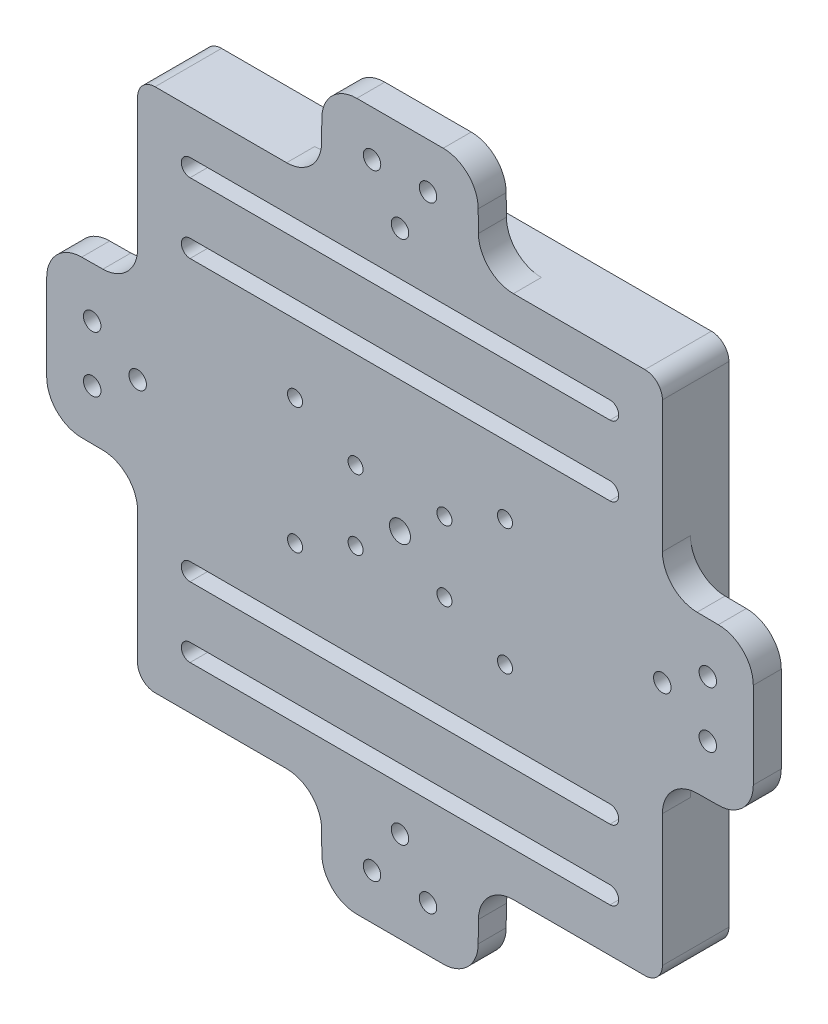
SolidWorks part; units mm, degrees
ref_plane "Front Plane" through (0, 0, 0) normal (0, 0, 1) x (1, 0, 0)
ref_plane "Top Plane" through (0, 0, 0) normal (0, 1, 0) x (1, 0, 0)
ref_plane "Right Plane" through (0, 0, 0) normal (1, 0, 0) x (0, 0, -1)
sketch "Sketch1" plane through (0, 0, 0) normal (0, 0, 1) x (1, 0, 0)
  line L13 (-90, -90) -> (90, -90)
  line L14 (-90, -90) -> (-90, 90)
  line L15 (-90, 90) -> (90, 90)
  line L16 (90, -90) -> (90, 90)
  line L17 (-90, -90) -> (90, 90) construction
  line L18 (-90, 90) -> (90, -90) construction
  line L19 (-75, -75) -> (75, -75)
  line L20 (-75, -75) -> (-75, 75)
  line L21 (-75, 75) -> (75, 75)
  line L22 (75, -75) -> (75, 75)
  line L23 (-75, -75) -> (75, 75) construction
  line L24 (-75, 75) -> (75, -75) construction
  line L39 (-75, -24.9122) -> (-75, 26.5574)
  line L40 (75, 22.5) -> (75, -22.5)
  line L41 (75, -22.5) -> (90.9698, -22.3479)
  line L42 (90.9698, -22.3479) -> (90.9698, 22.3479)
  line L43 (90.9698, 22.3479) -> (75, 22.5)
  line L44 (22.3479, -90.9698) -> (22.5, -75)
  line L45 (22.5, -75) -> (-22.5, -75)
  line L46 (-22.5, -75) -> (-22.3479, -90.9698)
  line L47 (-22.3479, -90.9698) -> (22.3479, -90.9698)
  line L48 (-90.9698, -22.3479) -> (-75, -22.5)
  line L49 (-75, -22.5) -> (-75, 22.5)
  line L50 (-75, 22.5) -> (-90.9698, 22.3479)
  line L51 (-90.9698, 22.3479) -> (-90.9698, -22.3479)
  line L52 (-22.3479, 90.9698) -> (-22.5, 75)
  line L53 (-22.5, 75) -> (22.5, 75)
  line L54 (22.5, 75) -> (22.3479, 90.9698)
  line L55 (22.3479, 90.9698) -> (-22.3479, 90.9698)
  line L64 (-72, -72) -> (-72, 72)
  line L65 (-72, 72) -> (72, 72)
  line L70 (72, -72) -> (72, 72)
  line L71 (-72, -72) -> (72, -72)
  line L72 (-10.5, -75) -> (10.5, -75)
  line L77 (75, -10.5) -> (64, -10.5)
  line L78 (75, -10.5) -> (75, 10.5)
  line L79 (75, 10.5) -> (64, 10.5)
  line L80 (64, -10.5) -> (64, 10.5)
  line L81 (-10.5, -75) -> (-10.5, -64)
  line L82 (-10.5, -64) -> (10.5, -64)
  line L83 (10.5, -75) -> (10.5, -64)
  line L84 (-75, 10.5) -> (-75, -10.5)
  line L85 (-75, 10.5) -> (-64, 10.5)
  line L86 (-64, 10.5) -> (-64, -10.5)
  line L87 (-75, -10.5) -> (-64, -10.5)
  line L88 (10.5, 75) -> (-10.5, 75)
  line L89 (10.5, 75) -> (10.5, 64)
  line L90 (10.5, 64) -> (-10.5, 64)
  line L91 (-10.5, 75) -> (-10.5, 64)
  line L92 (-75, 45) -> (-72, 45)
  line L93 (-45, 75) -> (-45, 72)
  circle A0 centre (87.9698, 8) radius 2.5
  circle A1 centre (74.9698, 0) radius 2.5
  circle A2 centre (87.9698, -8) radius 2.5
  circle A3 centre (8, -87.9698) radius 2.5
  circle A4 centre (0, -74.9698) radius 2.5
  circle A5 centre (-8, -87.9698) radius 2.5
  circle A6 centre (-87.9698, -8) radius 2.5
  circle A7 centre (-74.9698, 0) radius 2.5
  circle A8 centre (-87.9698, 8) radius 2.5
  circle A9 centre (-8, 87.9698) radius 2.5
  circle A10 centre (0, 74.9698) radius 2.5
  circle A11 centre (8, 87.9698) radius 2.5
  circle A12 centre (0, 0) radius 3
  point P0 (0, 0)
  point P11 (0, 0)
  point P74 (64, 0)
  point P85 (0, 0)
  dimension "D3" = 4
  dimension "D12" = 6
  dimension "D1" = 180
  dimension "D2" = 180
  dimension "D4" = 150
  dimension "D5" = 4
  dimension "D6" = 3
  dimension "D8" = 11
  dimension "D7" = 21
  dimension "D10" = 45
  dimension "D11" = 45
  dimension "D9" = 4
extrude "Boss-Extrude1" add sketch "Sketch1" along normal mid plane 8 contours L83 L19 L22 L77 L70 L71 | A2 L16 A0 L43 L22 L40 A1 L41 | L80 L77 L70 L79 | L91 L65 L64 L85 L86 L87 L71 L81 L82 L83 L70 L77 L80 L79 L89 L90 A12 | L21 L89 L65 L70 L79 L22 | L65 L91 L90 L89 | A10 L53 L91 L65 L89 | A11 L15 A9 L52 L21 L53 A10 L54 | A11 L15 L54 L55 L52 A9 | A8 L14 A6 L48 L39 L49 A7 L50 | L92 L20 L39 L85 L64 | L93 L21 L20 L92 L64 L65 | A5 L13 A3 L44 L19 L45 A4 L46 | A5 L13 L46 L47 L44 A3 | A4 L45 L83 L71 L81 | L71 L83 L82 L81 | A1 L40 L79 L70 L77 | A2 L16 L41 L42 L43 A0 | A8 L14 L50 L51 L48 A6 | L64 L87 L86 L85 | A7 L49 L87 L64 L85 | L87 L39 L20 L19 L81 L71 L64 | L21 L93 L65 L91 region at (0, -82.2708, 0) region at (0, -90.4981, 0) region at (-90.4981, 0, 0) region at (-82.2708, 0, 0) region at (-48.75, -74.0878, 0) region at (-10.2879, -73.5, 0) region at (-74.7879, -6.4999, 0) region at (0, -68, 0) region at (-41.25, -69.9635, 0) region at (-68, 0, 0) region at (41.25, -72.9122, 0) region at (-73.5, 27.75, 0) region at (82.2708, 0, 0) region at (90.4981, 0, 0) region at (0, 90.4981, 0) region at (0, 82.2708, 0) region at (-73.5, 45.4243, 0) region at (68, 0, 0) region at (72.2121, 0, 0) region at (-27.75, 73.5, 0) region at (72.9122, 41.25, 0) region at (-6.4999, 74.7879, 0) region at (0, 68, 0)
extrude "Boss-Extrude3" add sketch "Sketch1<4>" against normal blind 15 contours L93 L21 L20 L92 L64 L65 | L87 L39 L20 L19 L81 L71 L64 | L21 L89 L65 L70 L79 L22 | L83 L19 L22 L77 L70 L71 | L21 L93 L65 L91 | L92 L20 L39 L85 L64 region at (-48.75, -74.0878, 0) region at (41.25, -72.9122, 0) region at (-73.5, 27.75, 0) region at (-73.5, 45.4243, 0) region at (-27.75, 73.5, 0) region at (72.9122, 41.25, 0)
sketch "Sketch1<4>" plane through (0, 0, 0) normal (0, 0, 1) x (1, 0, 0) same geometry as "Sketch1"
sketch "Sketch6" plane through (0, 0, 0) normal (0, 0, 1) x (1, 0, 0)
  line L0 (-60, 60) -> (60, 60) construction
  line L1 (-60, 62.5) -> (60, 62.5)
  line L2 (-60, 57.5) -> (60, 57.5)
  line L3 (-60, 40) -> (60, 40) construction
  line L4 (-60, 42.5) -> (60, 42.5)
  line L5 (-60, 37.5) -> (60, 37.5)
  line L6 (-60, -40) -> (60, -40) construction
  line L7 (-60, -37.5) -> (60, -37.5)
  line L8 (-60, -42.5) -> (60, -42.5)
  line L9 (-60, -60) -> (60, -60) construction
  line L10 (-60, -57.5) -> (60, -57.5)
  line L11 (-60, -62.5) -> (60, -62.5)
  line L12 (-30, 18) -> (30, 18) construction
  line L14 (10.45, 0) -> (-10.45, 0) construction
  line L15 (-30, -18) -> (30, -18) construction
  line L17 (-12.7, -10) -> (12.7, -10) construction
  line L18 (-12.7, -10) -> (-12.7, 10) construction
  line L19 (-12.7, 10) -> (12.7, 10) construction
  line L20 (12.7, -10) -> (12.7, 10) construction
  line L21 (-12.7, -10) -> (12.7, 10) construction
  line L22 (-12.7, 10) -> (12.7, -10) construction
  arc A0 (-60, 62.5) -> (-60, 57.5) centre (-60, 60) ccw
  arc A1 (60, 57.5) -> (60, 62.5) centre (60, 60) ccw
  arc A2 (-60, 42.5) -> (-60, 37.5) centre (-60, 40) ccw
  arc A3 (60, 37.5) -> (60, 42.5) centre (60, 40) ccw
  arc A4 (-60, -37.5) -> (-60, -42.5) centre (-60, -40) ccw
  arc A5 (60, -42.5) -> (60, -37.5) centre (60, -40) ccw
  arc A6 (-60, -57.5) -> (-60, -62.5) centre (-60, -60) ccw
  arc A7 (60, -62.5) -> (60, -57.5) centre (60, -60) ccw
  circle A8 centre (30, 18) radius 2.15
  circle A9 centre (-30, 18) radius 2.15
  circle A10 centre (30, -18) radius 2.15
  circle A11 centre (-30, -18) radius 2.15
  circle A12 centre (-12.7, 10) radius 2.15
  circle A13 centre (-12.7, -10) radius 2.15
  circle A14 centre (12.7, -10) radius 2.15
  circle A15 centre (12.7, 10) radius 2.15
  point P2 (0, 60)
  point P8 (0, 40)
  point P15 (0, -40)
  point P22 (0, -60)
  point P32 (0, 18)
  point P41 (0, 0)
  dimension "D1" = 5
  dimension "D13" = 4.3
  dimension "D14" = 4.3
  dimension "D17" = 4.3
  dimension "D18" = 4.3
  dimension "D19" = 4.3
  dimension "D20" = 4.3
  dimension "D2" = 5
  dimension "D3" = 60
  dimension "D4" = 120
  dimension "D5" = 120
  dimension "D6" = 120
  dimension "D7" = 120
  dimension "D8" = 5
  dimension "D9" = 5
  dimension "D10" = 40
  dimension "D11" = 40
  dimension "D12" = 60
  dimension "D15" = 60
  dimension "D16" = 18
  dimension "D21" = 25.4
  dimension "D22" = 20
extrude "Cut-Extrude3" cut sketch "Sketch6" against normal mid plane 10
sketch "Sketch7" plane through (0, 0, 0) normal (0, 0, 1) x (1, 0, 0)
  line L0 (-90.9698, 22.3479) -> (-90.9698, -22.3479) construction
  line L1 (-100.9698, -22.3479) -> (-90.9698, -22.3479)
  line L2 (-100.9698, -22.3479) -> (-100.9698, 22.3479)
  line L3 (-100.9698, 22.3479) -> (-90.9698, 22.3479)
  line L4 (-90.9698, -22.3479) -> (-90.9698, 22.3479)
  line L5 (-100.9698, -22.3479) -> (-90.9698, 22.3479) construction
  line L6 (-100.9698, 22.3479) -> (-90.9698, -22.3479) construction
  line L7 (100.9698, -22.3479) -> (90.9698, -22.3479)
  line L8 (100.9698, -22.3479) -> (100.9698, 22.3479)
  line L9 (100.9698, 22.3479) -> (90.9698, 22.3479)
  line L10 (90.9698, -22.3479) -> (90.9698, 22.3479)
  line L11 (100.9698, -22.3479) -> (90.9698, 22.3479) construction
  line L12 (100.9698, 22.3479) -> (90.9698, -22.3479) construction
  line L17 (22.3479, 90.9698) -> (-22.3479, 90.9698) construction
  line L18 (-22.3479, 100.9698) -> (22.3479, 100.9698)
  line L19 (-22.3479, 100.9698) -> (-22.3479, 90.9698)
  line L20 (-22.3479, 90.9698) -> (22.3479, 90.9698)
  line L21 (22.3479, 100.9698) -> (22.3479, 90.9698)
  line L22 (-22.3479, 100.9698) -> (22.3479, 90.9698) construction
  line L23 (-22.3479, 90.9698) -> (22.3479, 100.9698) construction
  line L24 (22.3479, -100.9698) -> (-22.3479, -100.9698)
  line L25 (22.3479, -100.9698) -> (22.3479, -90.9698)
  line L26 (22.3479, -90.9698) -> (-22.3479, -90.9698)
  line L27 (-22.3479, -100.9698) -> (-22.3479, -90.9698)
  line L28 (22.3479, -100.9698) -> (-22.3479, -90.9698) construction
  line L29 (22.3479, -90.9698) -> (-22.3479, -100.9698) construction
  line L30 (90.9698, -22.3479) -> (90.9698, 22.3479) construction
  line L31 (-22.3479, -90.9698) -> (22.3479, -90.9698) construction
  point P0 (-95.9698, 0)
  point P6 (95.9698, 0)
  point P13 (0, -95.9698)
  point P17 (0, 95.9698)
  dimension "D1" = 10
  dimension "D2" = 44.6958
  dimension "D3" = 10
  dimension "D4" = 10
  dimension "D5" = 10
  dimension "D6" = 44.6958
  dimension "D7" = 44.6958
  dimension "D8" = 44.6958
extrude "Boss-Extrude4" add sketch "Sketch7" along normal up to surface (4 mm away) from surface contours L1 L4 L3 L2 | L21 L18 L19 L20 | L10 L7 L8 L9 | L27 L24 L25 L26 region at (-95.9698, 0, 0) region at (95.9698, 0, 0) region at (0, 95.9698, 0) region at (0, -95.9698, 0) up to face at (0, 60, 4) starting at face at (0, 60, -4)
fillet "Fillet1" radius 10 16 edges at (22.5, -75, 0) (-22.5, -75, 0) (-22.5, 75, 0) (22.5, 75, 0) (75, 22.5, 0) (75, -22.5, 0) (-75, -22.5, 0) (-75, 22.5, 0) (22.3479, 100.9698, 0) (-22.3479, 100.9698, 0) (-100.9698, 22.3479, 0) (-100.9698, -22.3479, 0) (-22.3479, -100.9698, 0) (22.3479, -100.9698, 0) (100.9698, -22.3479, 0) (100.9698, 22.3479, 0)
fillet "Fillet2" radius 5 4 edges at (-72, -72, -9.5) (-72, 72, -9.5) (72, -72, -9.5) (72, 72, -9.5)
fillet "Fillet3" radius 5 4 edges at (75, 75, -5.5) (-75, 75, -5.5) (-75, -75, -5.5) (75, -75, -5.5)
